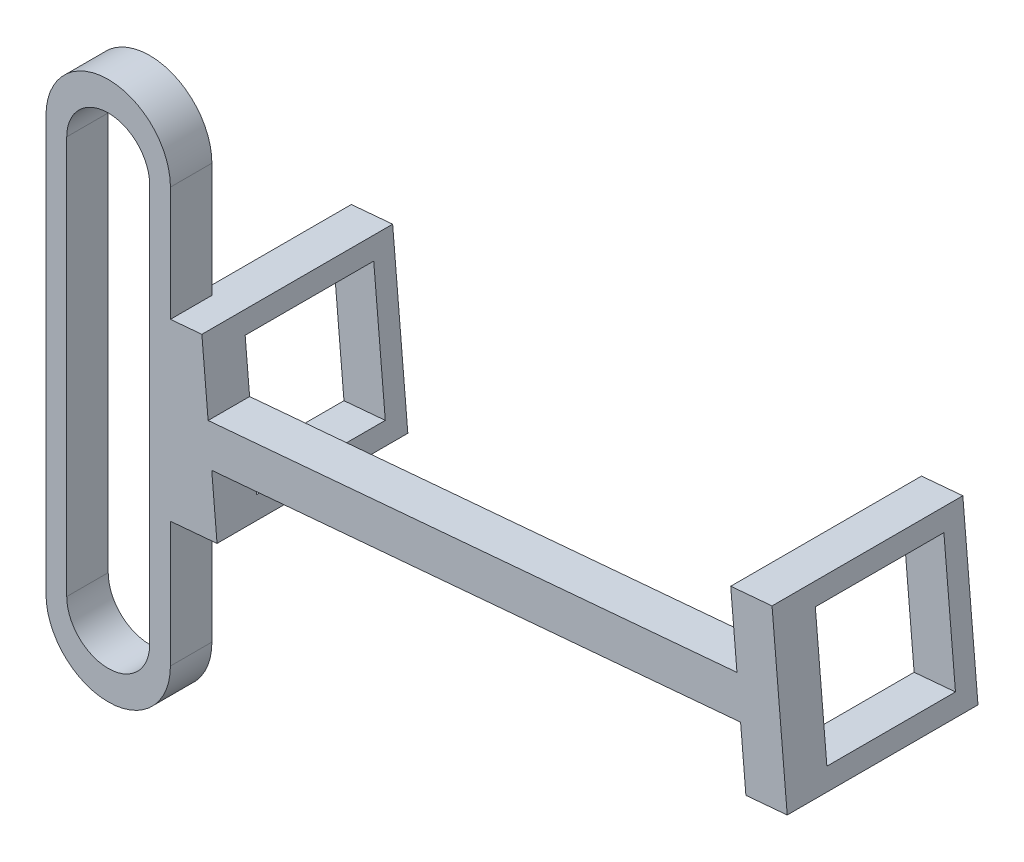
SolidWorks part; units mm, degrees
ref_plane "Front Plane" through (0, 0, 0) normal (0, 0, 1) x (1, 0, 0)
ref_plane "Top Plane" through (0, 0, 0) normal (0, 1, 0) x (1, 0, 0)
ref_plane "Right Plane" through (0, 0, 0) normal (1, 0, 0) x (0, 0, -1)
sketch "Sketch1" plane through (0, 0, 0) normal (0, 0, 1) x (1, 0, 0)
  line L1 (-9.525, -31.75) -> (9.525, -31.75)
  line L2 (-9.525, -31.75) -> (-9.525, 31.75)
  line L3 (-9.525, 31.75) -> (9.525, 31.75)
  line L4 (9.525, -31.75) -> (9.525, 31.75)
  line L5 (-9.525, -31.75) -> (9.525, 31.75) construction
  line L6 (-9.525, 31.75) -> (9.525, -31.75) construction
  circle A0 centre (0, 31.75) radius 9.525
  circle A1 centre (0, -31.75) radius 9.525
  point P0 (0, 0)
  dimension "D1" = 19.05
  dimension "D2" = 63.5
extrude "Boss-Extrude1" add sketch "Sketch1" along normal blind 6.35 contours A0 | L2 L1 L4 L3 | A1
sketch "Sketch2" plane through (0, 0, 6.35) normal (0, 0, 1) x (1, 0, 0)
  line L1 (-6.35, -30.48) -> (6.35, -30.48)
  line L2 (-6.35, -30.48) -> (-6.35, 30.48)
  line L3 (-6.35, 30.48) -> (6.35, 30.48)
  line L4 (6.35, -30.48) -> (6.35, 30.48)
  line L5 (-6.35, -30.48) -> (6.35, 30.48) construction
  line L6 (-6.35, 30.48) -> (6.35, -30.48) construction
  circle A0 centre (0, 30.48) radius 6.35
  circle A1 centre (0, -30.48) radius 6.35
  point P0 (0, 0)
  dimension "D1" = 12.7
  dimension "D2" = 60.96
extrude "Cut-Extrude1" cut sketch "Sketch2" against normal through all contours A0 | L2 L1 L4 L3 | A1
sketch "Sketch3" plane through (0, 0, 0) normal (0, 0, -1) x (-1, 0, 0)
  line L0 (-9.525, -31.75) -> (-9.525, 31.75) construction
  line L1 (-8.9716, 3.1387) -> (-102.5939, 11.3296)
  line L2 (-8.9716, 3.1387) -> (-9.525, -3.1871)
  line L3 (-9.525, -3.1871) -> (-103.1474, 5.0038)
  line L4 (-102.5939, 11.3296) -> (-103.1474, 5.0038)
  line L5 (-102.8707, 8.1667) -> (-9.525, 0) construction
  point P4 (-9.525, 0)
  point P5 (-9.525, 3.1384)
  point P8 (0, 0)
  dimension "D1" = 6.35
  dimension "D2" = 93.98
  dimension "D3" = 85
extrude "Boss-Extrude2" add sketch "Sketch3" against normal up to surface (6.35 mm away) up to face at (0, 0, 6.35)
ref_plane "Plane1" through (9.1759, 0.8028, 0) normal (-0.9962, -0.0872, 0) x (0, 0, 1)
sketch "Sketch4" plane through (-103.7124, 1291.1226, 0) normal (-0.9962, -0.0872, 0) x (0, 0, -1)
  line L1 (22.86, 1281.9136) -> (-6.35, 1281.9136)
  line L2 (22.86, 1281.9136) -> (22.86, 1308.5836)
  line L3 (22.86, 1308.5836) -> (-6.35, 1308.5836)
  line L4 (-6.35, 1281.9136) -> (-6.35, 1308.5836)
  line L5 (22.86, 1281.9136) -> (-6.35, 1308.5836) construction
  line L6 (22.86, 1308.5836) -> (-6.35, 1281.9136) construction
  line L7 (-6.35, 1292.9038) -> (-6.35, 1264.4496) construction
  line L8 (-6.35, 1326.0476) -> (-6.35, 1262.7893) construction
  point P0 (8.255, 1295.2486)
  point P5 (-6.35, 1308.5836)
  dimension "D1" = 29.21
  dimension "D2" = 26.67
extrude "Boss-Extrude3" add sketch "Sketch4" against normal blind 6.35
sketch "Sketch5" plane through (15.5018, 1.3562, 0) normal (0.9962, 0.0872, 0) x (0, 0, 1)
  line L0 (-22.86, 13.335) -> (-22.86, -13.335) construction
  line L1 (-19.685, -10.16) -> (0, -10.16)
  line L2 (-19.685, -10.16) -> (-19.685, 10.16)
  line L3 (-19.685, 10.16) -> (0, 10.16)
  line L4 (0, -10.16) -> (0, 10.16)
  line L5 (-19.685, -10.16) -> (0, 10.16) construction
  line L6 (-19.685, 10.16) -> (0, -10.16) construction
  line L7 (0, 32.4593) -> (0, 4.0052) construction
  point P0 (-9.8425, 0)
  point P5 (0, 10.16)
  dimension "D2" = 20.32
  dimension "D3" = 3.175
extrude "Cut-Extrude2" cut sketch "Sketch5" against normal through all contours L3 L4 L1 L2
sketch "Sketch6" plane through (102.7983, 8.9937, 0) normal (0.9962, 0.0872, 0) x (0, 0, -1)
  line L9 (-6.35, -4.0052) -> (-6.35, -13.335)
  line L10 (-6.35, -13.335) -> (22.86, -13.335)
  line L11 (22.86, -13.335) -> (22.86, 13.335)
  line L12 (22.86, 13.335) -> (-6.35, 13.335)
  line L17 (-6.35, -4.0052) -> (-6.35, -13.335)
  line L18 (-6.35, -13.335) -> (22.86, -13.335)
  line L19 (22.86, -13.335) -> (22.86, 13.335)
  line L20 (22.86, 13.335) -> (-6.35, 13.335)
  line L32 (-6.35, 2.3448) -> (0, 2.3448)
  line L33 (-6.35, 2.3448) -> (0, 2.3448)
  line L34 (-6.35, 13.335) -> (-6.35, 2.3448)
  line L35 (-6.35, 13.335) -> (-6.35, 2.3448)
  line L36 (0, -4.0052) -> (-6.35, -4.0052)
  line L37 (0, -4.0052) -> (-6.35, -4.0052)
  line L38 (19.685, -10.16) -> (0, -10.16)
  line L39 (19.685, -10.16) -> (0, -10.16)
  line L40 (0, -10.16) -> (0, -4.0052)
  line L41 (0, -10.16) -> (0, -4.0052)
  line L42 (0, 2.3448) -> (0, 10.16)
  line L43 (0, 2.3448) -> (0, 10.16)
  line L44 (0, 10.16) -> (19.685, 10.16)
  line L45 (0, 10.16) -> (19.685, 10.16)
  line L46 (19.685, 10.16) -> (19.685, -10.16)
  line L47 (19.685, 10.16) -> (19.685, -10.16)
  dimension "D1" = 0
extrude "Boss-Extrude4" add sketch "Sketch6" against normal blind 6.35
sketch "Sketch7" plane through (9.1759, 0.8028, 0) normal (-0.9962, -0.0872, 0) x (0, 0, 1)
  line L0 (0, -4.0052) -> (0, -13.335)
  line L1 (0, -30.799) -> (0, 32.4593) construction
  line L2 (-22.86, -13.335) -> (6.35, -13.335) construction
  line L3 (0, -13.335) -> (6.35, -13.335)
  line L4 (6.35, -30.799) -> (6.35, 32.4593) construction
  line L5 (6.35, -13.335) -> (6.35, -4.0052)
  line L6 (6.35, -4.0052) -> (0, -4.0052)
extrude "Boss-Extrude5" add sketch "Sketch7" along normal up to next
